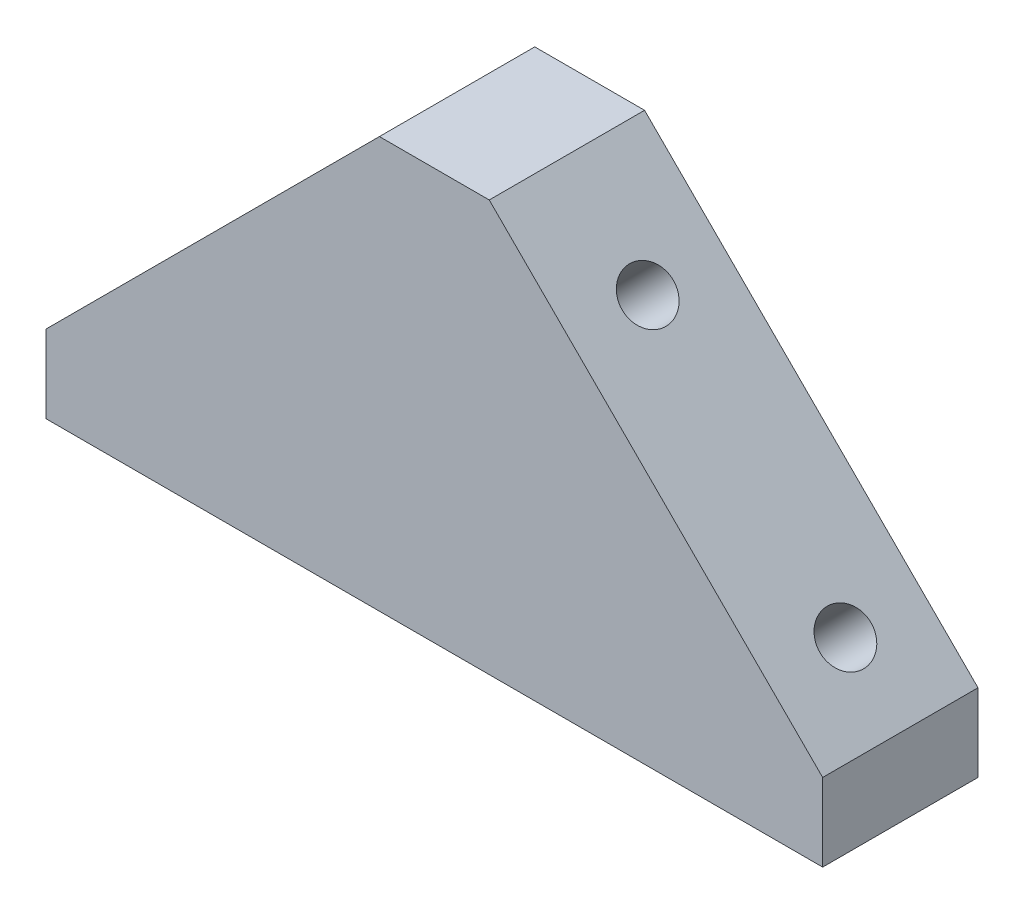
SolidWorks part; units mm, degrees
ref_plane "Front" through (0, 0, 0) normal (0, 0, 1) x (1, 0, 0)
ref_plane "Top" through (0, 0, 0) normal (0, 1, 0) x (1, 0, 0)
ref_plane "Right" through (0, 0, 0) normal (1, 0, 0) x (0, 0, -1)
sketch "Esquisse1" plane through (0, 0, 0) normal (0, 0, 1) x (1, 0, 0)
  line L0 (-25, 0) -> (25, 0)
  line L1 (25, 0) -> (25, 5)
  line L2 (25, 5) -> (0, 30)
  line L3 (0, 30) -> (0, 0) construction
  line L4 (-25, 5) -> (0, 30)
  line L5 (-25, 0) -> (-25, 5)
  point P5 (25, 2.5)
  dimension "D1" = 50
  dimension "D2" = 45
  dimension "D3" = 5
extrude "Boss.-Extru.1" add sketch "Esquisse1" along normal blind 10
sketch "Esquisse2" plane through (15, 15, 0) normal (0.7071, 0.7071, 0) x (0, 0, -1)
  line L0 (-5, -14.1421) -> (-5, 21.2132) construction
  line L1 (-10, -14.1421) -> (0, -14.1421) construction
  line L2 (-10, 21.2132) -> (0, 21.2132) construction
  circle A0 centre (-5, 8.8579) radius 1.65
  circle A1 centre (-5, -9.1421) radius 1.65
  dimension "D1" = 18
  dimension "D2" = 3.3
  dimension "D3" = 5
extrude "Enlèv. mat.-Extru.1" cut sketch "Esquisse2" against normal blind 8
sketch "Esquisse3" plane through (-15, 15, 0) normal (-0.7071, 0.7071, 0) x (0, 0, 1)
  line L0 (5, -14.1421) -> (5, 21.2132) construction
  line L1 (10, -14.1421) -> (0, -14.1421) construction
  line L2 (10, 21.2132) -> (0, 21.2132) construction
  circle A0 centre (5, 9.8579) radius 1.65
  circle A1 centre (5, -8.1421) radius 1.65
  dimension "D1" = 18
  dimension "D2" = 3.3
  dimension "D3" = 6
extrude "Enlèv. mat.-Extru.2" cut sketch "Esquisse3" against normal blind 8
chamfer "Chanfrein1" distance 5 angle 45 1 edges at (0, 30, 5)
sketch "Esquisse4" plane through (0, 0, 0) normal (0, -1, 0) x (1, 0, 0)
  line L0 (-25, 5) -> (25, 5) construction
  line L1 (-25, 10) -> (-25, 0) construction
  line L2 (25, 10) -> (25, 0) construction
  line L3 (0, 5) -> (0, 8.5239) construction
  circle A0 centre (0, 5) radius 1.65
  circle A1 centre (-16, 5) radius 1.65
  circle A2 centre (16, 5) radius 1.65
  dimension "D1" = 3.3
  dimension "D2" = 16
extrude "Enlèv. mat.-Extru.3" cut sketch "Esquisse4" against normal blind 10
